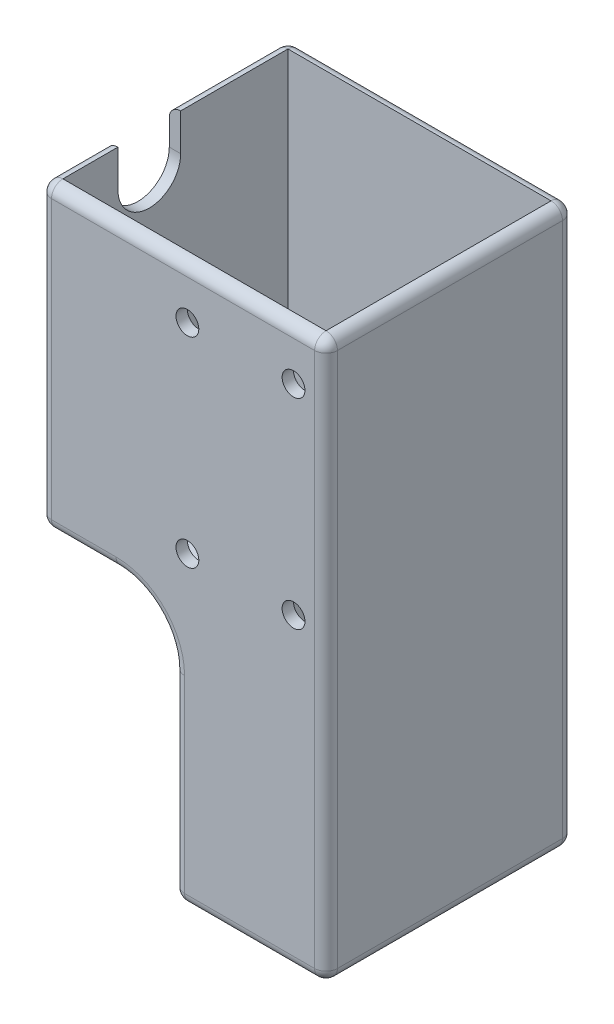
SolidWorks part; units mm, degrees
ref_plane "Front Plane" through (0, 0, 0) normal (0, 0, 1) x (1, 0, 0)
ref_plane "Top Plane" through (0, 0, 0) normal (0, 1, 0) x (1, 0, 0)
ref_plane "Right Plane" through (0, 0, 0) normal (1, 0, 0) x (0, 0, -1)
sketch "Sketch1" plane through (0, 0, 0) normal (0, 1, 0) x (1, 0, 0)
  line L1 (0, 0) -> (50.11, 0)
  line L2 (0, 0) -> (0, 43.44)
  line L3 (0, 43.44) -> (50.11, 43.44)
  line L4 (50.11, 0) -> (50.11, 43.44)
  dimension "D1" = 43.44
  dimension "D2" = 50.11
extrude "Boss-Extrude1" add sketch "Sketch1" along normal blind 97.79
sketch "Sketch2" plane through (0, 0, 0) normal (0, 0, 1) x (1, 0, 0)
  line L1 (0, 0) -> (23.32, 0)
  line L2 (0, 0) -> (0, 45.06)
  line L3 (0, 45.06) -> (23.32, 45.06)
  line L4 (23.32, 0) -> (23.32, 45.06)
  dimension "D1" = 23.32
  dimension "D2" = 45.06
extrude "Cut-Extrude1" cut sketch "Sketch2" against normal through all
shell "Shell1" thickness 2 removed face at (25.055, 97.79, -21.72)
sketch "Sketch4" plane through (0, 45.06, 0) normal (0, -1, 0) x (1, 0, 0)
  line L0 (25.32, -41.44) -> (2, -41.44) construction
  line L1 (1.1, -36.19) -> (7.6, -36.19)
  line L2 (1.1, -36.19) -> (1.1, -25.19)
  line L3 (1.1, -25.19) -> (7.6, -25.19)
  line L4 (7.6, -36.19) -> (7.6, -25.19)
  line L6 (0, -43.44) -> (0, 0) construction
  dimension "D1" = 5.25
  dimension "D2" = 11
  dimension "D3" = 6.5
  dimension "D4" = 1.1
extrude "Cut-Extrude2" cut sketch "Sketch4" against normal blind 2
sketch "Sketch6" plane through (0, 0, 0) normal (0, 0, 1) x (1, 0, 0)
  line L0 (0, 97.79) -> (50.11, 97.79) construction
  line L1 (48.11, 97.79) -> (48.11, 20.02) construction
  circle A0 centre (44.415, 88.885) radius 2
  circle A4 centre (25.815, 88.885) radius 2
  circle A5 centre (44.415, 53.805) radius 2
  circle A6 centre (25.815, 53.805) radius 2
  dimension "D1" = 4
  dimension "D2" = 8.905
  dimension "D3" = 3.695
  dimension "D4" = 4
  dimension "D5" = 18.6
  dimension "D6" = 8.905
  dimension "D7" = 4
  dimension "D8" = 3.695
  dimension "D10" = 4
  dimension "D11" = 18.6
  dimension "D9" = 43.985
  dimension "D12" = 43.985
extrude "Cut-Extrude3" cut sketch "Sketch6" against normal blind 2
sketch "Sketch7" plane through (0, 0, 0) normal (1, 0, 0) x (0, 0, -1)
  line L0 (41.44, 97.79) -> (41.44, 47.06) construction
  line L1 (43.44, 97.79) -> (0, 97.79) construction
  line L2 (22.64, 91.29) -> (22.64, 97.79)
  line L3 (22.64, 97.79) -> (11.64, 97.79)
  line L4 (11.64, 91.29) -> (11.64, 97.79)
  arc A0 (11.64, 91.29) -> (22.64, 91.29) centre (17.14, 91.29) ccw
  dimension "D3" = 11
  dimension "D1" = 24.3
  dimension "D2" = 6.5
extrude "Cut-Extrude5" cut sketch "Sketch7" along normal blind 2
sketch "Sketch8" plane through (0, 0, 0) normal (0, 1, 0) x (1, 0, 0)
  line L0 (36.715, 0) -> (36.715, 43.44) construction
  line L1 (23.32, 0) -> (50.11, 0) construction
  line L2 (50.11, 43.44) -> (23.32, 43.44) construction
  line L3 (23.32, 21.72) -> (50.11, 21.72) construction
  line L4 (23.32, 43.44) -> (23.32, 0) construction
  line L5 (50.11, 0) -> (50.11, 43.44) construction
  circle A0 centre (36.715, 21.72) radius 8.25
  dimension "D1" = 16.5
extrude "Cut-Extrude6" cut sketch "Sketch8" along normal up to surface (20.02 mm away) contours A0 up to face at (36.715, 20.02, -21.72)
fillet "Fillet1" radius 10 1 edges at (23.32, 45.06, -21.72)
fillet "Fillet2" radius 2 20 edges at (0, 45.06, -21.72) (0, 97.79, -5.82) (0, 71.425, 0) (0, 71.425, -43.44) (0, 97.79, -33.04) (6.66, 45.06, 0) (23.32, 17.53, 0) (23.32, 17.53, -43.44) (6.66, 45.06, -43.44) (50.11, 48.895, 0) (50.11, 97.79, -21.72) (50.11, 48.895, -43.44) (36.715, 0, 0) (50.11, 0, -21.72) (36.715, 0, -43.44) (23.32, 0, -21.72) (20.3911, 42.1311, 0) (20.3911, 42.1311, -43.44) (25.055, 97.79, 0) (25.055, 97.79, -43.44)
